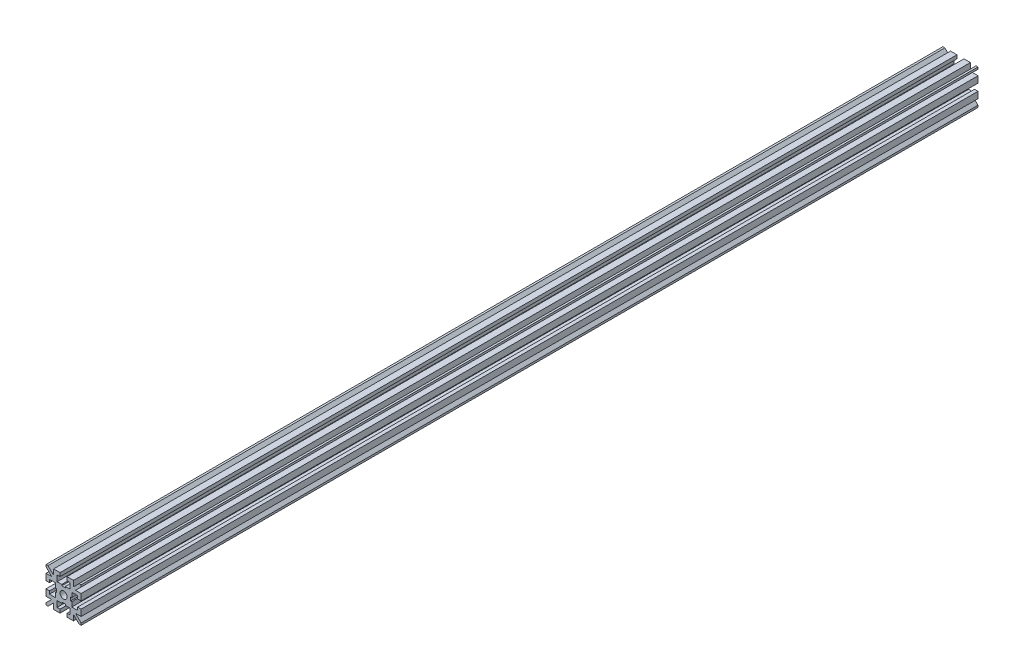
SolidWorks part; units mm, degrees
ref_plane "Front Plane" through (0, 0, 0) normal (0, 0, 1) x (1, 0, 0)
ref_plane "Top Plane" through (0, 0, 0) normal (0, 1, 0) x (1, 0, 0)
ref_plane "Right Plane" through (0, 0, 0) normal (1, 0, 0) x (0, 0, -1)
sketch "Sketch1" plane through (0, 0, 0) normal (0, 0, 1) x (1, 0, 0)
  line L1 (-9.0006, 3.7616) -> (5.9994, 3.7616)
  line L2 (-9.0006, 3.7616) -> (-9.0006, -11.2384)
  line L3 (-9.0006, -11.2384) -> (5.9994, -11.2384)
  line L4 (5.9994, 3.7616) -> (5.9994, -11.2384)
  dimension "D1" = 15
  dimension "D2" = 15
extrude "Boss-Extrude1" add sketch "Sketch1" along normal blind 383
sketch "Sketch2" plane through (0, 0, 383) normal (0, 0, 1) x (1, 0, 0)
  line L0 (-9.0006, 3.7616) -> (5.9994, -11.2384) construction
  line L1 (5.9994, 3.7616) -> (-9.0006, -11.2384) construction
  line L4 (1.9994, -4.4884) -> (1.9994, -6.4884)
  line L5 (5.9994, -3.7384) -> (1.9994, -3.7384) construction
  line L6 (5.9994, -11.2384) -> (5.9994, 3.7616) construction
  line L7 (-1.5006, 3.7616) -> (-1.5006, -3.7384) construction
  line L8 (5.9994, 3.7616) -> (-9.0006, 3.7616) construction
  line L9 (-9.0006, -3.7384) -> (-1.5006, -3.7384) construction
  line L10 (-9.0006, 3.7616) -> (-9.0006, -11.2384) construction
  line L11 (-1.5006, -11.2384) -> (-1.5006, -3.7384) construction
  line L12 (-9.0006, -11.2384) -> (5.9994, -11.2384) construction
  line L13 (1.9994, -4.4884) -> (1.4994, -4.4884)
  line L14 (1.9994, -0.9884) -> (4.4994, -0.9884)
  line L15 (1.9994, -0.9884) -> (1.9994, -2.9884)
  line L16 (1.9994, -6.4884) -> (4.4994, -6.4884)
  line L17 (4.4994, -0.9884) -> (4.4994, -6.4884)
  line L18 (-4.2506, -7.2384) -> (-4.2506, -9.7384)
  line L19 (1.9994, -2.9884) -> (1.4994, -2.9884)
  line L20 (1.4994, -4.4884) -> (1.4994, -2.9884)
  line L21 (1.4994, -3.7384) -> (-0.0006, -3.7384) construction
  line L22 (-2.2506, -7.2384) -> (-4.2506, -7.2384)
  line L23 (-2.2506, -7.2384) -> (-2.2506, -6.7384)
  line L24 (-2.2506, -6.7384) -> (-0.7506, -6.7384)
  line L25 (-0.7506, -7.2384) -> (-0.7506, -6.7384)
  line L26 (1.2494, -7.2384) -> (-0.7506, -7.2384)
  line L27 (1.2494, -7.2384) -> (1.2494, -9.7384)
  line L28 (1.2494, -9.7384) -> (-4.2506, -9.7384)
  line L29 (-5.0006, -0.9884) -> (-7.5006, -0.9884)
  line L30 (-5.0006, -2.9884) -> (-5.0006, -0.9884)
  line L31 (-5.0006, -2.9884) -> (-4.5006, -2.9884)
  line L32 (-4.5006, -2.9884) -> (-4.5006, -4.4884)
  line L33 (-5.0006, -4.4884) -> (-4.5006, -4.4884)
  line L34 (-5.0006, -6.4884) -> (-5.0006, -4.4884)
  line L35 (-5.0006, -6.4884) -> (-7.5006, -6.4884)
  line L36 (-7.5006, -6.4884) -> (-7.5006, -0.9884)
  line L37 (1.2494, -0.2384) -> (1.2494, 2.2616)
  line L38 (-0.7506, -0.2384) -> (1.2494, -0.2384)
  line L39 (-0.7506, -0.2384) -> (-0.7506, -0.7384)
  line L40 (-0.7506, -0.7384) -> (-2.2506, -0.7384)
  line L41 (-2.2506, -0.2384) -> (-2.2506, -0.7384)
  line L42 (-4.2506, -0.2384) -> (-2.2506, -0.2384)
  line L43 (-4.2506, -0.2384) -> (-4.2506, 2.2616)
  line L44 (-4.2506, 2.2616) -> (1.2494, 2.2616)
  circle A0 centre (-1.5006, -3.7384) radius 1.5
  point P60 (-1.5006, -3.7384)
  dimension "D1" = 5.5
  dimension "D2" = 2.5
  dimension "D3" = 1.5
  dimension "D4" = 2.75
  dimension "D5" = 0.5
  dimension "D6" = 1.5
  dimension "D7" = 0.75
  dimension "D8" = 4
extrude "Cut-Extrude1" cut sketch "Sketch2" against normal up to surface (383 mm away) up to face at (-1.5006, -3.7384, 0)
sketch "Sketch3" plane through (0, 0, 383) normal (0, 0, 1) x (1, 0, 0)
  line L0 (5.9994, 3.7616) -> (-9.0006, -11.2384) construction
  line L1 (-9.0006, 3.7616) -> (5.9994, -11.2384) construction
  line L2 (5.1509, 3.7616) -> (2.7494, 1.3602)
  line L3 (5.9994, 3.7616) -> (-9.0006, 3.7616) construction
  line L4 (2.7494, 1.3602) -> (2.7494, 3.7616)
  line L5 (2.7494, 3.7616) -> (5.1509, 3.7616)
  line L6 (1.2494, -0.2384) -> (1.2494, 2.2616) construction
  line L7 (5.9994, 0.5116) -> (5.9994, 2.9131)
  line L8 (3.5979, 0.5116) -> (5.9994, 0.5116)
  line L9 (5.9994, 2.9131) -> (3.5979, 0.5116)
  line L10 (1.2494, 2.2616) -> (-4.2506, 2.2616) construction
  line L11 (-3.0006, 3.7616) -> (-0.0006, 3.7616)
  line L12 (-3.0006, 3.7616) -> (-3.0006, 2.2616)
  line L13 (-3.0006, 2.2616) -> (-0.0006, 2.2616)
  line L14 (-0.0006, 3.7616) -> (-0.0006, 2.2616)
  line L15 (-2.2506, -0.7384) -> (-0.7506, -0.7384) construction
  line L16 (2.7494, -8.8369) -> (2.7494, -11.2384)
  line L17 (2.7494, -11.2384) -> (5.1509, -11.2384)
  line L18 (5.1509, -11.2384) -> (2.7494, -8.8369)
  line L19 (5.9994, -10.3898) -> (3.5979, -7.9884)
  line L20 (3.5979, -7.9884) -> (5.9994, -7.9884)
  line L21 (5.9994, -7.9884) -> (5.9994, -10.3898)
  line L22 (5.9994, -5.2384) -> (4.4994, -5.2384)
  line L23 (5.9994, -2.2384) -> (5.9994, -5.2384)
  line L24 (5.9994, -2.2384) -> (4.4994, -2.2384)
  line L25 (4.4994, -2.2384) -> (4.4994, -5.2384)
  line L26 (-6.5991, -7.9884) -> (-9.0006, -7.9884)
  line L27 (-9.0006, -7.9884) -> (-9.0006, -10.3898)
  line L28 (-9.0006, -10.3898) -> (-6.5991, -7.9884)
  line L29 (-8.1521, -11.2384) -> (-5.7506, -8.8369)
  line L30 (-5.7506, -8.8369) -> (-5.7506, -11.2384)
  line L31 (-5.7506, -11.2384) -> (-8.1521, -11.2384)
  line L32 (-3.0006, -11.2384) -> (-3.0006, -9.7384)
  line L33 (-0.0006, -11.2384) -> (-3.0006, -11.2384)
  line L34 (-0.0006, -11.2384) -> (-0.0006, -9.7384)
  line L35 (-0.0006, -9.7384) -> (-3.0006, -9.7384)
  line L36 (-5.7506, 1.3602) -> (-5.7506, 3.7616)
  line L37 (-5.7506, 3.7616) -> (-8.1521, 3.7616)
  line L38 (-8.1521, 3.7616) -> (-5.7506, 1.3602)
  line L39 (-9.0006, 2.9131) -> (-6.5991, 0.5116)
  line L40 (-6.5991, 0.5116) -> (-9.0006, 0.5116)
  line L41 (-9.0006, 0.5116) -> (-9.0006, 2.9131)
  line L42 (-9.0006, -2.2384) -> (-7.5006, -2.2384)
  line L43 (-9.0006, -5.2384) -> (-9.0006, -2.2384)
  line L44 (-9.0006, -5.2384) -> (-7.5006, -5.2384)
  line L45 (-7.5006, -5.2384) -> (-7.5006, -2.2384)
  point P24 (-1.5006, -0.7384)
  point P27 (-1.5006, -3.7384)
  point P61 (-1.5006, -3.7384)
  dimension "D1" = 0.6
  dimension "D2" = 1.5
  dimension "D3" = 3
  dimension "D4" = 1.5
  dimension "D5" = 4
extrude "Cut-Extrude2" cut sketch "Sketch3" against normal up to surface (383 mm away) up to face at (-1.5006, 0.2616, 0)
